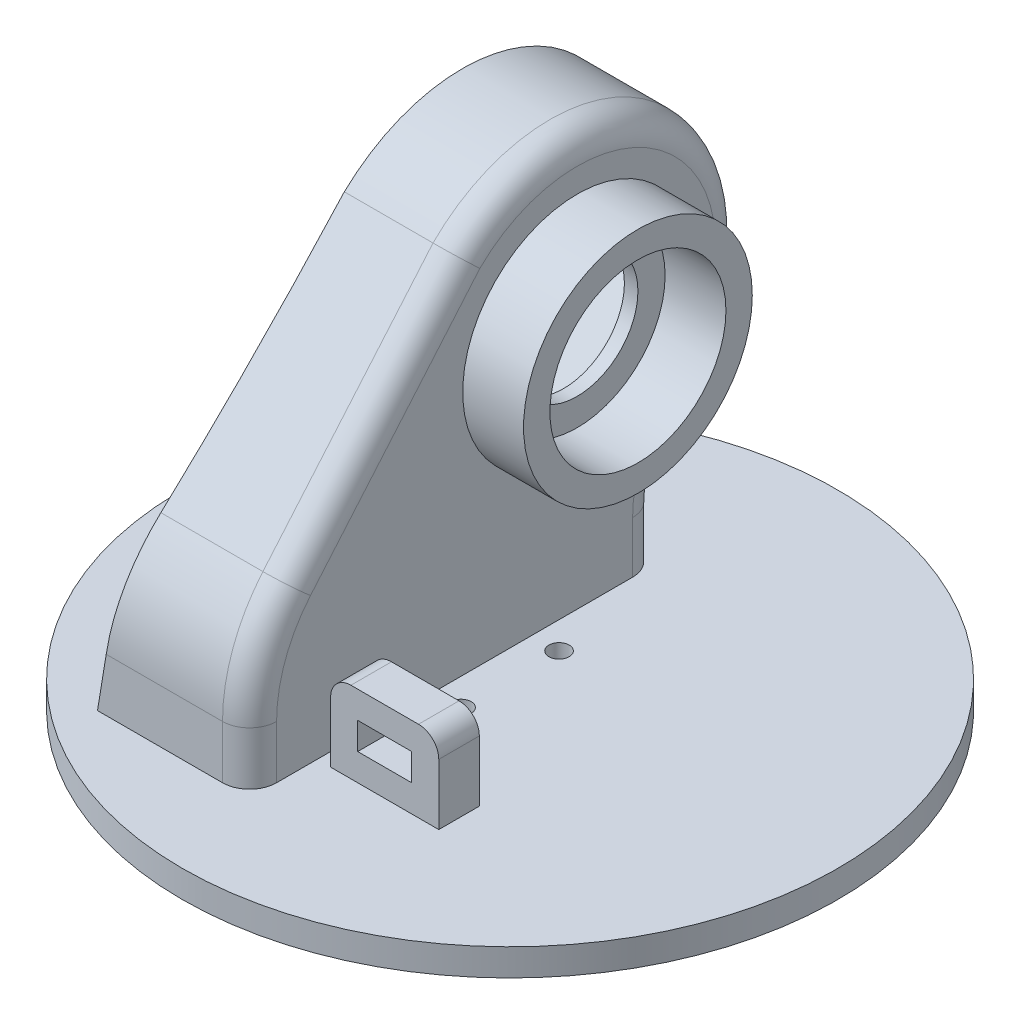
SolidWorks part; units mm, degrees
ref_plane "Front Plane" through (0, 0, 0) normal (0, 0, 1) x (1, 0, 0)
ref_plane "Top Plane" through (0, 0, 0) normal (0, 1, 0) x (1, 0, 0)
ref_plane "Right Plane" through (0, 0, 0) normal (1, 0, 0) x (0, 0, -1)
sketch "Sketch2" plane through (0, 0, 0) normal (0, 1, 0) x (1, 0, 0)
  circle A0 centre (0, 0) radius 48.5
  dimension "D1" = 97
extrude "Boss-Extrude1" add sketch "Sketch2" along normal blind 4
sketch "Sketch4" plane through (0, 0, 0) normal (0, -1, 0) x (1, 0, 0)
  circle A0 centre (0, 7.25) radius 1.5
  circle A1 centre (0, -7.25) radius 1.5
  dimension "D1" = 3
  dimension "D2" = 3
  dimension "D3" = 14.5
  dimension "D4" = 7.25
extrude "Cut-Extrude2" cut sketch "Sketch4" against normal through all
sketch "Sketch5" plane through (0, 0, 0) normal (0, -1, 0) x (1, 0, 0)
  circle A0 centre (0, 0) radius 3.75
  dimension "D1" = 7.5
extrude "Cut-Extrude3" cut sketch "Sketch5" against normal blind 1.5
ref_plane "Plane1" through (-4, 0, 0) normal (1, 0, 0) x (0, 0, -1)
sketch "Sketch7" plane through (-4, 0, 0) normal (1, 0, 0) x (0, 0, -1)
  line L0 (23.1299, 11.6445) -> (23.1299, 4)
  line L5 (48.5, 4) -> (-48.5, 4) construction
  line L6 (-27.2273, 29.5362) -> (-1.2843, 55.4793)
  line L7 (-43.5609, 4) -> (23.1299, 4)
  line L11 (-34.5496, 4) -> (-34.5496, 11.8586)
  arc A4 (28.7298, 24.692) -> (-1.2843, 55.4793) centre (13.9185, 40.2765) ccw
  arc A5 (28.7298, 24.692) -> (23.1299, 11.6445) centre (41.1299, 11.6445) ccw
  arc A6 (-27.2273, 29.5362) -> (-34.5496, 11.8586) centre (-9.5496, 11.8586) ccw
  dimension "D1" = 25
  dimension "D4" = 43
  dimension "D3" = 18
  dimension "D5" = 45
extrude "Boss-Extrude2" add sketch "Sketch7" against normal blind 14 contours A5 A4 L6 L7 L0 | A4 | A4 | A4 | L6 A6 L7 region at (-4, 29.3392, -2.7362)
ref_plane "Plane2" through (-6, 0, 0) normal (1, 0, 0) x (0, 0, -1)
sketch "Sketch8" plane through (-6, 0, 0) normal (1, 0, 0) x (0, 0, -1)
  line L0 (-27.2273, 29.5362) -> (-1.2843, 55.4793) construction
  line L1 (-15.2496, 25.9576) -> (13.7417, 54.9489)
  line L2 (-15.2496, 25.9576) -> (-0.4004, 11.1083)
  line L3 (-0.4004, 11.1083) -> (28.591, 40.0997)
  line L4 (13.7417, 54.9489) -> (28.591, 40.0997)
  line L5 (-15.2496, 25.9576) -> (28.591, 40.0997) construction
  line L6 (-0.4004, 11.1083) -> (13.7417, 54.9489) construction
  point P0 (6.6707, 33.0286)
  point P11 (13.9185, 40.2765)
  dimension "D1" = 41
  dimension "D2" = 21
  dimension "D3" = 90
  dimension "D4" = 20.5
  dimension "D5" = 90
  dimension "D6" = 10.25
  dimension "D7" = 10.5
extrude "Cut-Extrude5" cut sketch "Sketch8" against normal up to next
sketch "Sketch9" plane through (-18, 0, 0) normal (-1, 0, 0) x (0, 0, 1)
  line L0 (-13.7417, 54.9489) -> (-28.591, 40.0997) construction
  line L3 (-21.1664, 47.5243) -> (-22.536, 48.894) construction
  circle A0 centre (-20.1057, 53.5347) radius 1.3
  circle A1 centre (-27.1768, 46.4637) radius 1.3
  circle A2 centre (6.7644, 12.5225) radius 1.3
  circle A3 centre (13.8354, 19.5936) radius 1.3
  dimension "D1" = 2.6
  dimension "D5" = 5
  dimension "D6" = 90
  dimension "D2" = 3.5
  dimension "D3" = 2
  dimension "D4" = 2
extrude "Cut-Extrude6" cut sketch "Sketch9" against normal blind 7.5
sketch "Sketch11" plane through (-4, 0, 0) normal (1, 0, 0) x (0, 0, -1)
  circle A0 centre (13.9185, 40.2765) radius 9
  dimension "D1" = 18
extrude "Cut-Extrude9" cut sketch "Sketch11" against normal up to next
sketch "Sketch17" plane through (-18, 0, 0) normal (-1, 0, 0) x (0, 0, 1)
  line L0 (29.3486, 31.6576) -> (3.4056, 57.6006)
  line L1 (-26.1299, 11.6445) -> (-26.1299, 1)
  line L2 (-26.1299, 1) -> (37.5496, 1)
  line L3 (37.5496, 1) -> (37.5496, 11.8586)
  line L4 (27.2273, 29.5362) -> (1.2843, 55.4793)
  line L5 (-23.1299, 11.6445) -> (-23.1299, 4)
  line L6 (-23.1299, 4) -> (34.5496, 4)
  line L7 (34.5496, 4) -> (34.5496, 11.8586)
  line L9 (-23.1299, 11.6445) -> (-23.1299, 4)
  line L10 (-23.1299, 4) -> (34.5496, 4)
  line L11 (34.5496, 4) -> (34.5496, 11.8586)
  line L12 (-26.1299, 4) -> (37.5496, 4)
  line L13 (48.5, 4) -> (-48.5, 4) construction
  line L14 (3.4056, 57.6006) -> (28.5745, 28.0776)
  line L15 (1.2843, 55.4793) -> (26.295, 26.1272)
  line L16 (31.5496, 11.8586) -> (31.5496, 4)
  line L18 (27.2273, 29.5362) -> (1.2843, 55.4793) construction
  arc A0 (3.4056, 57.6006) -> (-30.7965, 22.5174) centre (-13.9185, 40.2765) ccw
  arc A1 (-26.1299, 11.6445) -> (-30.7965, 22.5174) centre (-41.1299, 11.6445) ccw
  arc A2 (37.5496, 11.8586) -> (29.3486, 31.6576) centre (9.5496, 11.8586) ccw
  arc A3 (1.2843, 55.4793) -> (-28.7298, 24.692) centre (-13.9185, 40.2765) ccw
  arc A4 (-23.1299, 11.6445) -> (-28.7298, 24.692) centre (-41.1299, 11.6445) ccw
  arc A5 (34.5496, 11.8586) -> (27.2273, 29.5362) centre (9.5496, 11.8586) ccw
  arc A6 (1.2843, 55.4793) -> (-28.7298, 24.692) centre (-13.9185, 40.2765) ccw
  arc A7 (-23.1299, 11.6445) -> (-28.7298, 24.692) centre (-41.1299, 11.6445) ccw
  arc A8 (34.5496, 11.8586) -> (27.2273, 29.5362) centre (9.5496, 11.8586) ccw
  arc A9 (31.5496, 11.8586) -> (25.106, 27.4149) centre (9.5496, 11.8586) ccw
  line M16 (27.2273, 29.5362) -> (1.2843, 55.4793)
  arc M17 (1.2843, 55.4793) -> (-28.7298, 24.692) centre (-13.9185, 40.2765) ccw
  arc M18 (-28.7298, 24.692) -> (-23.1299, 11.6445) centre (-41.1299, 11.6445) cw
  line M19 (-23.1299, 11.6445) -> (-23.1299, 4)
  line M21 (34.5496, 4) -> (34.5496, 11.8586)
  arc M22 (34.5496, 11.8586) -> (27.2273, 29.5362) centre (9.5496, 11.8586) ccw
  dimension "D1" = 0
  dimension "D2" = 3
  dimension "D3" = 3
extrude "Boss-Extrude7" add sketch "Sketch17" along normal blind 9 and the other way up to surface (14 mm away) contours A9 L16 L12 L15 M21 M22 M16 | A1 L1 L12 L14 A0 M19 M18 M17 M16 M22 region at (-18, 42.2523, 15.3017) region at (-18, 20.289, 32.4332) other way up to face at (-4, 40.2765, -22.9185)
sketch "Sketch25" plane through (-18, 0, 0) normal (-1, 0, 0) x (0, 0, 1)
  line L0 (-23.1299, 11.6445) -> (-23.1299, 4)
  line L1 (48.5, 4) -> (-48.5, 4) construction
  line L2 (-23.1299, 11.6445) -> (-23.1299, 4) construction
  line L3 (1.2843, 55.4793) -> (26.295, 26.1272) construction
  line L4 (31.5496, 4) -> (-23.1299, 4) construction
  line L5 (31.5496, 11.8586) -> (31.5496, 4) construction
  line L6 (31.5496, 4) -> (-23.1299, 4)
  line L7 (31.5496, 11.8586) -> (31.5496, 4)
  line L8 (1.2843, 55.4793) -> (26.295, 26.1272)
  arc A0 (-23.1299, 11.6445) -> (-28.7298, 24.692) centre (-41.1299, 11.6445) ccw construction
  arc A1 (1.2843, 55.4793) -> (-28.7298, 24.692) centre (-13.9185, 40.2765) ccw construction
  arc A2 (-23.1299, 11.6445) -> (-28.7298, 24.692) centre (-41.1299, 11.6445) ccw
  arc A3 (31.5496, 11.8586) -> (26.295, 26.1272) centre (9.5496, 11.8586) ccw construction
  arc A4 (31.5496, 11.8586) -> (26.295, 26.1272) centre (9.5496, 11.8586) ccw
  spline S0 degree 3 poles (-28.7298, 24.692) (-21.9549, 18.2532) (-19.0941, 12.798) (-15.1299, 4) knots 0 0 0 0 1 1 1 1
  spline S1 degree 2 poles (11.7516, 43.195) (26.5513, 25.8264) (25.5496, 4) knots 0 0 0 1 1 1
  dimension "D2" = 8
  dimension "D1" = 6
extrude "Boss-Extrude10" add sketch "Sketch25" along normal up to surface (9 mm away) contours S0 L6 L0 A2 | A4 S1 A2 S0 L8 region at (-18, 9.918, -20.706) region at (-18, 17.2593, 26.6261) up to face at (-27, 22.2911, 0.3951)
sketch "Sketch26" plane through (0, 0, 0) normal (0, 0, 1) x (1, 0, 0)
  line L0 (-4, 64.7765) -> (-27, 64.7765) construction
  line L1 (-27, 4) -> (-4, 4) construction
  line L2 (-27, 4) -> (-27, 11.8586) construction
  line L3 (-26, 64.7765) -> (-27, 64.7765)
  line L4 (-27, 64.7765) -> (-27, 4)
  line L5 (-27, 4) -> (-23, 4)
  spline S0 degree 2 poles (-26, 64.7765) (-24.7724, 34.3751) (-23, 4) knots 0 0 0 1 1 1
  dimension "D1" = 1
  dimension "D2" = 4
  dimension "D3" = 2
extrude "Cut-Extrude15" [suppressed] cut sketch "Sketch26" against normal through all both and the other way through all contours L4 L5 S0 L3
sketch "Sketch27" plane through (0, 4, 0) normal (0, 1, 0) x (1, 0, 0)
  line L1 (-2, -18.5496) -> (14, -18.5496)
  line L2 (-2, -18.5496) -> (-2, -24.5496)
  line L3 (-2, -24.5496) -> (14, -24.5496)
  line L4 (14, -18.5496) -> (14, -24.5496)
  line L5 (-27, -34.5496) -> (-4, -34.5496) construction
  line L6 (-4, -34.5496) -> (-4, 26.1299) construction
  dimension "D1" = 10
  dimension "D2" = 6
  dimension "D3" = 16
  dimension "D4" = 2
extrude "Boss-Extrude11" add sketch "Sketch27" along normal blind 12
fillet "Fillet6" radius 3 2 edges at (14, 16, 21.5496) (-2, 16, 21.5496)
sketch "Sketch28" plane through (0, 0, 24.5496) normal (0, 0, 1) x (1, 0, 0)
  line L8 (10, 12) -> (2, 12)
  line L9 (2, 12) -> (2, 8)
  line L10 (2, 8) -> (10, 8)
  line L11 (10, 8) -> (10, 12)
  line L12 (10, 12) -> (2, 12)
  line L13 (2, 12) -> (2, 8)
  line L14 (2, 8) -> (10, 8)
  line L15 (10, 8) -> (10, 12)
  dimension "D1" = 4
extrude "Cut-Extrude16" cut sketch "Sketch28" against normal up to next
sketch "Sketch29" plane through (0, 0, 0) normal (0, 0, 1) x (1, 0, 0)
  line L0 (-4, 64.7765) -> (-27, 64.7765) construction
  line L1 (-27, 4) -> (-4, 4) construction
  line L2 (-21, 64.7765) -> (-27, 64.7765)
  line L3 (-27, 64.7765) -> (-27, 4)
  line L4 (-27, 4) -> (-26.5, 4)
  line L5 (48.5, 4) -> (-48.5, 4) construction
  spline S0 degree 2 poles (-21, 64.7765) (-21.2205, 34.1409) (-26.5, 4) knots 0 0 0 1 1 1
  dimension "D1" = 6
  dimension "D2" = 4
  dimension "D3" = 0.5
  dimension "D4" = 25
extrude "Cut-Extrude17" cut sketch "Sketch29" against normal through all both and the other way through all
sketch "Sketch30" plane through (-4, 0, 0) normal (1, 0, 0) x (0, 0, -1)
  circle A0 centre (13.9185, 40.2765) radius 13.025
  circle A1 centre (13.9185, 40.2765) radius 16.925
  dimension "D1" = 3.9
  dimension "D2" = 26.05
extrude "Boss-Extrude12" add sketch "Sketch30" along normal blind 9
ref_plane "Plane3" through (0, 13.179, 13.179) normal (0, -0.7071, -0.7071) x (-1, 0, 0)
sketch "Sketch31" plane through (0, 13.179, 13.179) normal (0, -0.7071, -0.7071) x (-1, 0, 0)
  line L0 (18, 48.5716) -> (18, 56.5716)
  line L1 (18, 56.5716) -> (15, 48.5716)
  line L2 (15, 48.5716) -> (18, 48.5716)
  line L3 (18, 7.5716) -> (15, 7.5716)
  line L4 (18, 7.5716) -> (18, 48.5716)
  line L5 (18, 48.5716) -> (6, 48.5716)
  line L6 (6, 48.5716) -> (6, 7.5716)
  line L7 (6, 7.5716) -> (18, 7.5716)
  line L8 (18, 7.5716) -> (18, 48.5716)
  line L9 (18, 48.5716) -> (6, 48.5716)
  line L10 (6, 48.5716) -> (6, 7.5716)
  line L11 (6, 7.5716) -> (18, 7.5716)
  line L12 (15, 7.5716) -> (18, -0.4284)
  line L13 (18, -0.4284) -> (18, 7.5716)
  dimension "D2" = 8
  dimension "D3" = 3
  dimension "D4" = 8
  dimension "D5" = 3
  dimension "D1" = 0
extrude "Cut-Extrude18" cut sketch "Sketch31" against normal mid plane 2 contours L3 L12 L13 | L0 L1 L2
fillet "Fillet7" radius 4 6 edges at (-4, 7.8223, -26.1299) (-4, 17.5605, -27.3459) (-4, 7.9293, 34.5496) (-4, 20.5009, 33.0083) (-4, 57.3789, -31.4615) (-4, 42.8391, 15.99)
